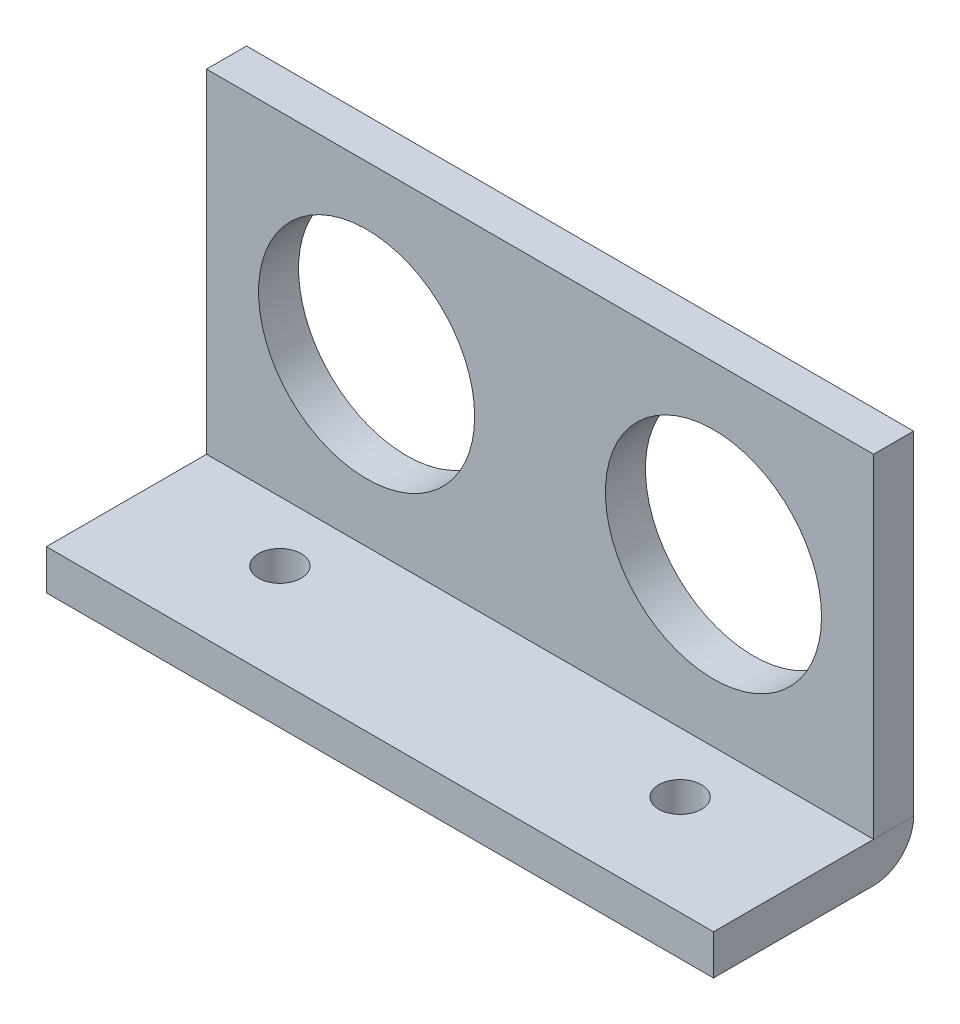
SolidWorks part; units mm, degrees
ref_plane "Front Plane" through (0, 0, 0) normal (0, 0, 1) x (1, 0, 0)
ref_plane "Top Plane" through (0, 0, 0) normal (0, 1, 0) x (1, 0, 0)
ref_plane "Right Plane" through (0, 0, 0) normal (1, 0, 0) x (0, 0, -1)
sketch "Sketch1" plane through (0, 0, 0) normal (0, 1, 0) x (1, 0, 0)
  line L0 (0, 0) -> (0, 66.1205) construction
  line L1 (-25, 7.5) -> (25, 7.5)
  line L2 (-25, 7.5) -> (-25, -7.5)
  line L3 (-25, -7.5) -> (25, -7.5)
  line L4 (25, 7.5) -> (25, -7.5)
  circle A0 centre (-15, 0) radius 1.6
  circle A1 centre (15, 0) radius 1.6
  point P0 (0, 0)
  point P12 (0, 0)
  dimension "D3" = 15
  dimension "D1" = 15
  dimension "D2" = 50
  dimension "D4" = 15
extrude "Boss-Extrude1" add sketch "Sketch1" along normal blind 3
sketch "Sketch3" plane through (0, 3, 0) normal (0, 1, 0) x (1, 0, 0)
  line L0 (25, 7.5) -> (-25, 7.5) construction
  line L1 (-25, 4.5) -> (25, 4.5)
  line L2 (-25, 4.5) -> (-25, 7.5)
  line L3 (-25, 7.5) -> (25, 7.5)
  line L4 (25, 4.5) -> (25, 7.5)
  point P4 (-25, 10.5)
  dimension "D1" = 3
extrude "Boss-Extrude3" add sketch "Sketch3" along normal blind 25 separate body
sketch "Sketch4" plane through (0, 0, -4.5) normal (0, 0, 1) x (1, 0, 0)
  line L1 (0, -1000) -> (0, 49000) construction
  line L5 (0, 15.5) -> (-38.4472, 15.5) construction
  circle A0 centre (-13, 15.5) radius 8.1
  circle A1 centre (13, 15.5) radius 8.1
  dimension "D1" = 13
  dimension "D2" = 13
extrude "Cut-Extrude1" cut sketch "Sketch4" against normal through all
fillet "Fillet8" radius 3 1 edges at (0, 0, -7.5)
